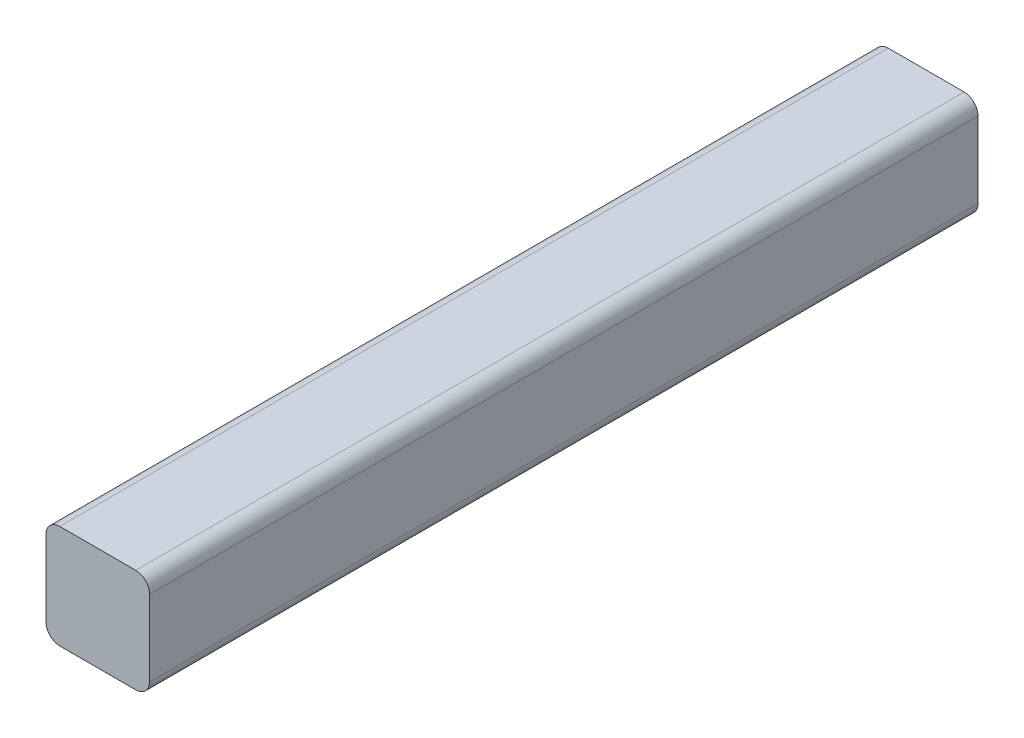
SolidWorks part; units mm, degrees
ref_plane "Front Plane" through (0, 0, 0) normal (0, 0, 1) x (1, 0, 0)
ref_plane "Top Plane" through (0, 0, 0) normal (0, 1, 0) x (1, 0, 0)
ref_plane "Right Plane" through (0, 0, 0) normal (1, 0, 0) x (0, 0, -1)
sketch "Sketch1" plane through (0, 0, 0) normal (0, 0, 1) x (1, 0, 0)
  line L1 (-9.525, -9.525) -> (9.525, -9.525)
  line L2 (-9.525, -9.525) -> (-9.525, 9.525)
  line L3 (-9.525, 9.525) -> (9.525, 9.525)
  line L4 (9.525, -9.525) -> (9.525, 9.525)
  line L5 (-9.525, -9.525) -> (9.525, 9.525) construction
  line L6 (-9.525, 9.525) -> (9.525, -9.525) construction
  point P0 (0, 0)
  dimension "D1" = 19.05
extrude "Boss-Extrude1" add sketch "Sketch1" along normal mid plane 152.4
fillet "Fillet1" radius 2.54 4 edges at (9.525, 9.525, 0) (-9.525, 9.525, 0) (-9.525, -9.525, 0) (9.525, -9.525, 0)
